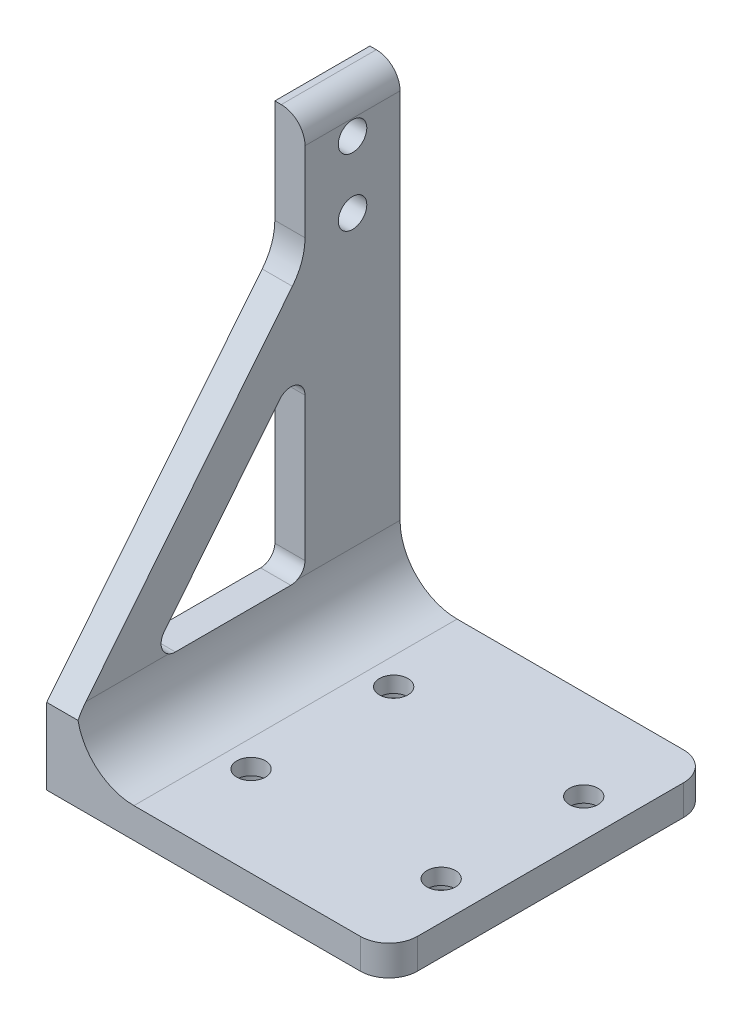
SolidWorks part; units mm, degrees
ref_plane "Front Plane" through (0, 0, 0) normal (0, 0, 1) x (1, 0, 0)
ref_plane "Top Plane" through (0, 0, 0) normal (0, 1, 0) x (1, 0, 0)
ref_plane "Right Plane" through (0, 0, 0) normal (1, 0, 0) x (0, 0, -1)
sketch "Sketch1" plane through (0, 0, 0) normal (0, 0, 1) x (1, 0, 0)
  line L0 (0, 0) -> (0, 50.8)
  line L1 (0, 0) -> (36, 0)
  line L2 (3.175, 3.175) -> (36, 3.175)
  line L3 (3.175, 3.175) -> (3.175, 50.8)
  line L4 (0, 50.8) -> (3.175, 50.8)
  line L5 (36, 0) -> (36, 3.175)
  dimension "D1" = 50.8
  dimension "D2" = 36
  dimension "D3" = 3.175
extrude "Boss-Extrude1" add sketch "Sketch1" along normal blind 17 and the other way blind 17
fillet "Fillet1" radius 6 1 edges at (3.175, 3.175, 0)
fillet "Fillet2" radius 2.5 1 edges at (3.175, 50.8, 0)
sketch "Sketch4" plane through (0, 0, 0) normal (0, -1, 0) x (1, 0, 0)
  line L0 (36, -17) -> (36, 17) construction
  circle A4 centre (12, -7.5) radius 1.5
  circle A5 centre (12, 7.5) radius 1.5
  circle A6 centre (32, -7.5) radius 1.5
  circle A7 centre (32, 7.5) radius 1.5
  dimension "D1" = 20
  dimension "D2" = 20
  dimension "D3" = 4
  dimension "D4" = 4
extrude "Cut-Extrude2" cut sketch "Sketch4" against normal blind 10
sketch "Sketch5" plane through (0, 0, 0) normal (0, -1, 0) x (1, 0, 0)
  circle A0 centre (12, 7.5) radius 3.025
  circle A1 centre (32, 7.5) radius 3.025
  circle A2 centre (12, -7.5) radius 3.025
  circle A3 centre (32, -7.5) radius 3.025
  dimension "D1" = 6.05
extrude "Cut-Extrude3" cut sketch "Sketch5" against normal blind 1.5
sketch "Sketch6" plane through (0, 0, 0) normal (-1, 0, 0) x (0, 0, 1)
  line L0 (17, 50.8) -> (-7, 50.8)
  line L1 (-17, 50.8) -> (17, 50.8) construction
  line L2 (-17, 50.8) -> (-17, 0) construction
  line L3 (-7, 50.8) -> (-7, 37.8)
  line L4 (-7, 37.8) -> (17, 8)
  line L5 (17, 50.8) -> (17, 0) construction
  dimension "D1" = 10
  dimension "D3" = 8
extrude "Cut-Extrude4" cut sketch "Sketch6" against normal blind 4 and the other way through all
fillet "Fillet3" radius 3 2 edges at (36, 1.5875, -17) (36, 1.5875, 17)
fillet "Fillet4" radius 6 1 edges at (1.5875, 37.8, -7)
sketch "Sketch7" plane through (0, 0, 0) normal (-1, 0, 0) x (0, 0, 1)
  line L0 (-7, 29.8286) -> (-7, 9)
  line L2 (-7, 9) -> (9.7747, 9)
  line L6 (-9.5671, 33.016) -> (13.1059, 4.8638)
  line L7 (-7, 29.8286) -> (9.7747, 9)
  line L8 (-17, 0) -> (17, 0) construction
  dimension "D1" = 5
  dimension "D2" = 9
extrude "Cut-Extrude5" cut sketch "Sketch7" against normal blind 5
fillet "Fillet5" radius 1.5 3 edges at (1.5875, 29.8286, -7) (1.5888, 9, 9.7747) (1.5888, 9, -7)
sketch "Sketch8" plane through (0, 0, 0) normal (-1, 0, 0) x (0, 0, 1)
  line L0 (-12, 50.8) -> (-12, 41.175) construction
  line L1 (-17, 50.8) -> (-7, 50.8) construction
  circle A4 centre (-12, 46.675) radius 1.5
  circle A5 centre (-12, 39.675) radius 1.5
extrude "Cut-Extrude8" cut sketch "Sketch8" against normal blind 10
